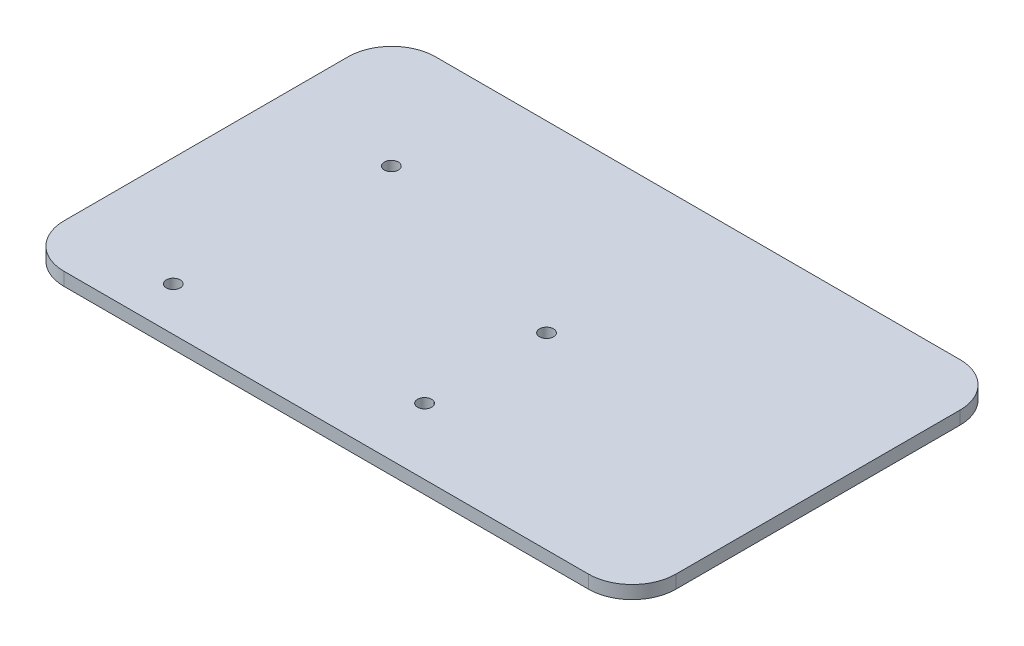
SolidWorks part; units mm, degrees
ref_plane "Front Plane" through (0, 0, 0) normal (0, 0, 1) x (1, 0, 0)
ref_plane "Top Plane" through (0, 0, 0) normal (0, 1, 0) x (1, 0, 0)
ref_plane "Right Plane" through (0, 0, 0) normal (1, 0, 0) x (0, 0, -1)
sketch "Sketch3" plane through (0, 0, 0) normal (0, 1, 0) x (1, 0, 0)
  line L1 (-70, 42.5) -> (70, 42.5)
  line L2 (-70, 42.5) -> (-70, -42.5)
  line L3 (-70, -42.5) -> (70, -42.5)
  line L4 (70, 42.5) -> (70, -42.5)
  line L5 (-70, 42.5) -> (70, -42.5) construction
  line L6 (-70, -42.5) -> (70, 42.5) construction
  point P0 (0, 0)
  dimension "D1" = 140
  dimension "D2" = 85
extrude "Boss-Extrude1" add sketch "Sketch3" along normal blind 3 contours L1 L4 L3 L2
sketch "Sketch4" plane through (0, 3, 0) normal (0, 1, 0) x (1, 0, 0)
  line L1 (-70, 42.5) -> (-70, -42.5) construction
  line L2 (-70, -42.5) -> (70, -42.5) construction
  line L3 (-45, 15.8) -> (-45, -32.5) construction
  line L5 (-70, 42.5) -> (-70, -42.5) construction
  line L6 (7.4, 0.5) -> (7.4, -27.4) construction
  line L7 (70, 42.5) -> (70, -42.5) construction
  circle A0 centre (-43.4, 15.8) radius 1.6
  circle A1 centre (7.4, 0.5) radius 1.6
  circle A2 centre (-45, -32.5) radius 1.6
  circle A3 centre (7.4, -27.4) radius 1.6
  dimension "D1" = 3.2
  dimension "D2" = 25
  dimension "D3" = 10
  dimension "D4" = 48.3
  dimension "D5" = 5.1
  dimension "D6" = 27.9
  dimension "D7" = 50.8
extrude "Cut-Extrude1" cut sketch "Sketch4" against normal blind 3
sketch "Sketch5" [suppressed] plane through (0, 3, 0) normal (0, 1, 0) x (1, 0, 0)
  line L0 (-47, -47) -> (47, -47) construction
  line L1 (21.45, -2.8) -> (33.45, -2.8)
  line L2 (21.45, -2.8) -> (21.45, 11.2)
  line L3 (21.45, 11.2) -> (33.45, 11.2)
  line L4 (33.45, -2.8) -> (33.45, 11.2)
  line L5 (47, 47) -> (47, -47) construction
  dimension "D1" = 12
  dimension "D2" = 14
  dimension "D3" = 44.2
  dimension "D4" = 13.55
extrude "Cut-Extrude2" [suppressed] cut sketch "Sketch5" against normal blind 10
sketch "Sketch6" [suppressed] plane through (0, 3, 0) normal (0, 1, 0) x (1, 0, 0)
  line L0 (-47, 47) -> (47, 47) construction
  line L1 (22.2, 30) -> (32.7, 30)
  line L2 (22.2, 30) -> (22.2, 39)
  line L3 (22.2, 39) -> (32.7, 39)
  line L4 (32.7, 30) -> (32.7, 39)
  line L5 (47, 47) -> (47, -47) construction
  dimension "D1" = 9
  dimension "D2" = 10.5
  dimension "D3" = 8
  dimension "D4" = 14.3
extrude "Cut-Extrude3" [suppressed] cut sketch "Sketch6" against normal blind 10
fillet "Fillet1" radius 10 1 edges at (-70, 1.5, 42.5)
fillet "Fillet2" radius 10 1 edges at (-70, 1.5, -42.5)
fillet "Fillet3" radius 10 1 edges at (70, 1.5, -42.5)
fillet "Fillet4" radius 10 1 edges at (70, 1.5, 42.5)
